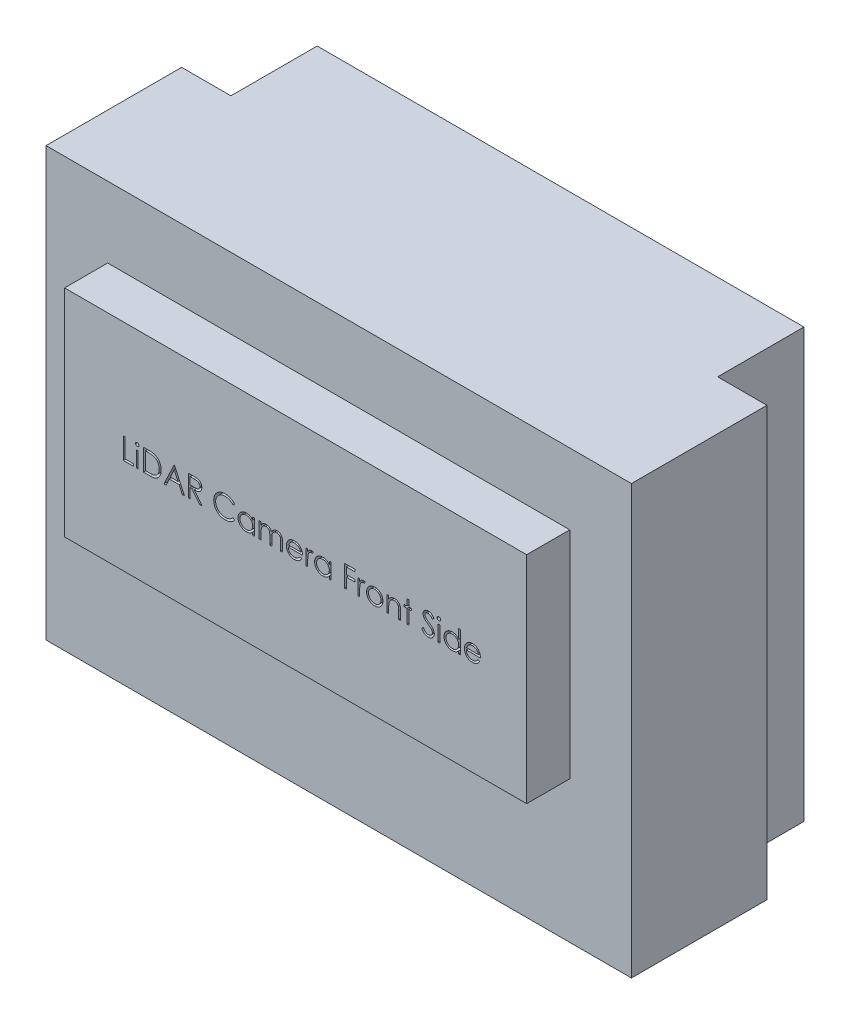
SolidWorks part; units mm, degrees
ref_plane "Front Plane" through (0, 0, 0) normal (0, 0, 1) x (1, 0, 0)
ref_plane "Top Plane" through (0, 0, 0) normal (0, 1, 0) x (1, 0, 0)
ref_plane "Right Plane" through (0, 0, 0) normal (1, 0, 0) x (0, 0, -1)
sketch "Sketch1" plane through (0, 0, 0) normal (0, 0, 1) x (1, 0, 0)
  line L1 (0, 0) -> (95, 0)
  line L2 (0, 0) -> (0, 69.5)
  line L3 (0, 69.5) -> (95, 69.5)
  line L4 (95, 0) -> (95, 69.5)
  dimension "D1" = 95
  dimension "D2" = 69.5
extrude "Body" add sketch "Sketch1" along normal blind 22
sketch "Sketch2" plane through (0, 0, 22) normal (0, 0, 1) x (1, 0, 0)
  line L1 (10, 58) -> (85, 58)
  line L2 (10, 58) -> (10, 23)
  line L3 (10, 23) -> (85, 23)
  line L4 (85, 58) -> (85, 23)
  line L5 (0, 69.5) -> (0, 0) construction
  line L7 (95, 69.5) -> (0, 69.5) construction
  point P6 (0, 0)
  dimension "D1" = 35
  dimension "D2" = 75
  dimension "D3" = 10
  dimension "D4" = 11.5
extrude "Camera Pop Out" add sketch "Sketch2" along normal blind 7 contours L2 L1 L4 L3
sketch "Sketch3" plane through (0, 0, 0) normal (0, 0, -1) x (-1, 0, 0)
  line L0 (-95, 69.5) -> (0, 69.5) construction
  line L1 (-87, 69.5) -> (-8, 69.5)
  line L2 (-87, 69.5) -> (-87, 0)
  line L3 (-87, 0) -> (-8, 0)
  line L4 (-8, 69.5) -> (-8, 0)
  line L5 (-95, 0) -> (-95, 69.5) construction
  dimension "D1" = 79
  dimension "D2" = 69.5
  dimension "D3" = 0
  dimension "D4" = 8
extrude "back side" add sketch "Sketch3" along normal blind 14 contours L2 L1 L4 L3
sketch "Text" plane through (0, 0, 29) normal (0, 0, 1) x (1, 0, 0)
  text T0 "LiDAR Camera Front Side\r\n             " font "Century Gothic" height 3.5
  point P1 (31.6, 38.4192)
  point P2 (0, 0)
  point P3 (24.1674, 39.4542)
  point P4 (0, 0)
  point P5 (16.8289, 38.137)
  point P6 (17.3934, 37.7607)
extrude "Cut-Extrude1" cut sketch "Text" against normal blind 2
